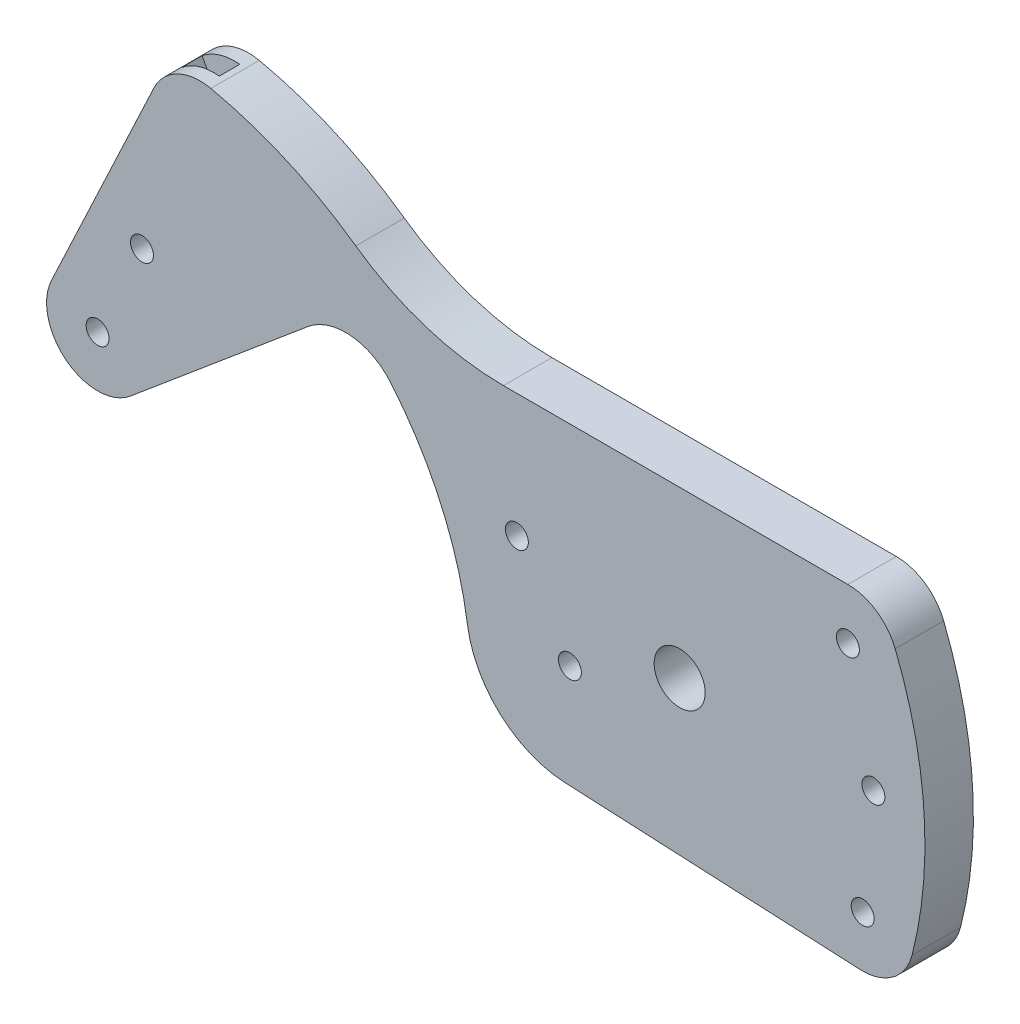
SolidWorks part; units mm, degrees
ref_plane "Front Plane" through (0, 0, 0) normal (0, 0, 1) x (1, 0, 0)
ref_plane "Top Plane" through (0, 0, 0) normal (0, 1, 0) x (1, 0, 0)
ref_plane "Right Plane" through (0, 0, 0) normal (1, 0, 0) x (0, 0, -1)
sketch "Sketch1" plane through (0, 0, 0) normal (0, 0, 1) x (1, 0, 0)
  line L1 (-5, -5) -> (5, -5) construction
  line L2 (-5, -5) -> (-5, 5) construction
  line L3 (-5, 5) -> (5, 5) construction
  line L4 (5, -5) -> (5, 5) construction
  line L5 (-5, -5) -> (5, 5) construction
  line L6 (-5, 5) -> (5, -5) construction
  line L7 (35.3984, -31.7883) -> (-22.5002, -28.984)
  line L9 (-114.4671, 24.4556) -> (-123.1671, 5.9556)
  line L10 (-107.6899, -5.9604) -> (-72.8648, 23.2613)
  line L11 (-114.4671, 24.4556) -> (-103.0859, 48.6569)
  line L16 (-65.4725, 14.4515) -> (-108.3178, -21.5) construction
  line L17 (50.9822, -33.5) -> (-177.2181, -33.5) construction
  line L20 (-34.5382, 32.4) -> (32.9822, 32.4)
  circle A0 centre (0, 0) radius 5
  circle A1 centre (-31.9178, 8.2) radius 2.25
  circle A2 centre (-21.5178, -8.7) radius 2.25
  circle A3 centre (32.9822, 22.4) radius 2.25
  circle A4 centre (37.9822, -0.1) radius 2.25
  circle A5 centre (35.8822, -21.8) radius 2.25
  circle A6 centre (35.8822, -21.8) radius 2.25 construction
  circle A7 centre (37.9822, -0.1) radius 2.25 construction
  circle A8 centre (32.9822, 22.4) radius 2.25 construction
  circle A9 centre (-31.9178, 8.2) radius 2.25 construction
  circle A10 centre (-21.5178, -8.7) radius 2.25 construction
  arc A12 (-41.6083, -11.6627) -> (-22.5002, -28.984) centre (-21.5178, -8.7) ccw
  arc A13 (32.5913, -31.6523) -> (28.0429, 32.4) centre (-33.3577, -4.1478) ccw construction
  arc A14 (45.5723, -24.2704) -> (42.2664, 26.1153) centre (-33.3577, -4.1478) ccw
  arc A15 (35.3984, -31.7883) -> (45.5723, -24.2704) centre (35.8822, -21.8) ccw
  arc A16 (42.2664, 26.1153) -> (32.9822, 32.4) centre (32.9822, 22.4) ccw
  circle A17 centre (-105.4178, 20.2) radius 2.25
  circle A18 centre (-33.3577, -4.1478) radius 81.4546 construction
  circle A19 centre (-114.1178, 1.7) radius 2.25
  circle A21 centre (-105.4178, 20.2) radius 2.25 construction
  circle A22 centre (-114.1178, 1.7) radius 2.25 construction
  circle A23 centre (-105.4178, 20.2) radius 10 construction
  arc A24 (-123.1671, 5.9556) -> (-107.6899, -5.9604) centre (-114.1178, 1.7) ccw
  arc A27 (-91.9187, 54.1744) -> (-103.0859, 48.6569) centre (-94.0366, 44.4013) ccw
  circle A31 centre (-33.3577, -4.1478) radius 71.4546 construction
  arc A32 (-41.6083, -11.6627) -> (-56.6627, 21.8438) centre (-108.3178, -21.5) ccw
  arc A33 (-31.0568, -26.628) -> (-91.9187, 54.1744) centre (-108.3178, -21.5) ccw
  arc A34 (-63.487, 41.6328) -> (-34.5382, 32.4) centre (-34.5382, 82.4) ccw
  arc A35 (-56.6627, 21.8438) -> (-72.8648, 23.2613) centre (-65.4725, 14.4515) ccw
  circle A36 centre (-65.4725, 14.4515) radius 10.5004 construction
  circle A37 centre (-108.3178, -21.5) radius 67.4309 construction
  circle A38 centre (-108.3178, -21.5) radius 77.4309 construction
  circle A39 centre (-108.3178, -21.5) radius 10.5004 construction
  circle A40 centre (-108.3178, -21.5) radius 11.5004 construction
  circle A41 centre (0, 0) radius 33 construction
  point P35 (50.3427, -4.5217)
  point P37 (37.1696, 16.7103)
  point P54 (-36.0565, -0.0269)
  point P75 (-40.8381, -1.4887)
  dimension "D1" = 10
  dimension "D3" = 10
  dimension "D5" = 50
  dimension "D7" = 40
  dimension "D4" = 10
  dimension "D2" = 10
  dimension "D8" = 1
extrude "Boss-Extrude1" add sketch "Sketch1" along normal mid plane 9.5 contours A0 L4 L3 | A0 L1 L4 | A0 L2 L1 | A0 L3 L2 | A35 A32 A12 A33 A27 L11 L9 A24 L10 A17 A19 region at (6.5137, -29.0519, 0) region at (-82.595, 21.4109, 0)
sketch "Sketch2" plane through (0, 0, 0) normal (0, 0, 1) x (1, 0, 0)
  line L0 (-94.0366, 44.4013) -> (-96.9145, 53.9782) construction
  line L1 (-78.2271, 18.7618) -> (-72.8648, 23.2613)
  line L2 (-94.0366, 44.4013) -> (-84.6999, 13.3304) construction
  line L3 (-92.0846, 44.9879) -> (-78.2271, 18.7618)
  line L4 (-95.0124, 54.3536) -> (-94.0366, 44.4013) construction
  line L5 (-94.0366, 44.4013) -> (-90.5122, 8.4534) construction
  line L6 (-98.7084, 53.2429) -> (-94.0366, 44.4013) construction
  line L7 (-94.0366, 44.4013) -> (-79.7943, 17.4467) construction
  line L8 (-100.3823, 52.1299) -> (-95.9887, 43.8147)
  line L9 (-93.0022, 54.3476) -> (-92.0846, 44.9879)
  line L12 (-92.369, 6.8953) -> (-78.2271, 18.7618)
  line L13 (-107.6899, -5.9604) -> (-72.8648, 23.2613) construction
  line L14 (-101.3327, 53.9285) -> (-91.0539, 34.4751) construction
  line L15 (-93.2007, 56.3721) -> (-91.0539, 34.4751) construction
  line L16 (-95.9887, 43.8147) -> (-92.369, 6.8953)
  line L18 (-97.0194, 54.3274) -> (-78.2271, 18.7618) construction
  line L19 (-97.0194, 54.3274) -> (-92.369, 6.8953) construction
  line L20 (-92.369, 6.8953) -> (-107.6899, -5.9604)
  line L22 (-94.0366, 44.4013) -> (-90.3786, 7.0905) construction
  line L23 (-94.0366, 44.4013) -> (-79.9955, 17.8274) construction
  arc A0 (-93.0022, 54.3476) -> (-100.3823, 52.1299) centre (-94.0366, 44.4013) ccw
  arc A1 (-95.0124, 54.3536) -> (-98.7084, 53.2429) centre (-94.0366, 44.4013) ccw construction
  arc A2 (-93.2007, 56.3721) -> (-101.3327, 53.9285) centre (-94.0366, 44.4013) ccw construction
  arc A3 (-91.9187, 54.1744) -> (-103.0859, 48.6569) centre (-94.0366, 44.4013) ccw construction
  point P33 (-96.9145, 53.9782)
  dimension "D3" = 7
  dimension "D4" = 20
  dimension "D1" = 2
  dimension "D2" = 2
extrude "Cut-Extrude1" cut sketch "Sketch2" against normal mid plane 4 contours A0 L8 L12 L9 region at (-89.8285, 28.8905, 0)
